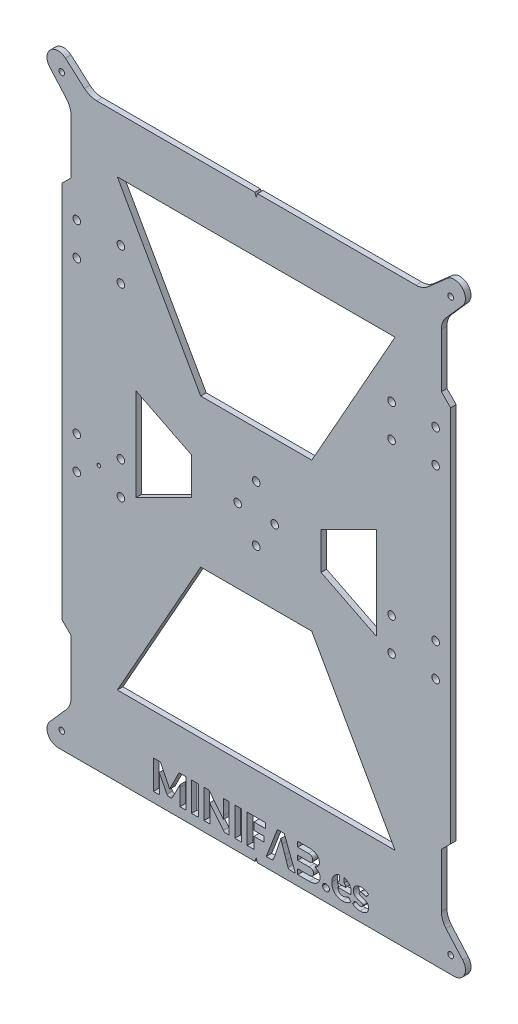
SolidWorks part; units mm, degrees
ref_plane "Front Plane" through (0, 0, 0) normal (0, 0, 1) x (1, 0, 0)
ref_plane "Top Plane" through (0, 0, 0) normal (0, 1, 0) x (1, 0, 0)
ref_plane "Right Plane" through (0, 0, 0) normal (1, 0, 0) x (0, 0, -1)
sketch "Model" plane through (0, 0, 0) normal (0, 0, 1) x (1, 0, 0)
  line L0 (52.095, -156.4121) -> (52.8612, -155.1609)
  line L1 (60.6553, -147.8549) -> (59.9077, -149.0226)
  line L2 (5.4072, -157.6632) -> (11.4282, -142.044)
  line L3 (8.2277, -157.6632) -> (5.4072, -157.6632)
  line L4 (10.3191, -154.1044) -> (9.4016, -156.8693)
  line L5 (11.1501, -151.7319) -> (10.3191, -154.1044)
  line L6 (12.5835, -147.4811) -> (11.1501, -151.7319)
  line L7 (15.4102, -151.7319) -> (13.9706, -147.4594)
  line L8 (16.235, -154.1044) -> (15.4102, -151.7319)
  line L9 (17.1525, -156.8693) -> (16.235, -154.1044)
  line L10 (21.1439, -157.6632) -> (18.3481, -157.6632)
  line L11 (15.1229, -142.044) -> (21.1439, -157.6632)
  line L12 (11.4282, -142.044) -> (15.1229, -142.044)
  line L13 (-11.5929, -157.6632) -> (-11.5929, -142.044)
  line L14 (-7.963, -157.6632) -> (-11.5929, -157.6632)
  line L15 (-7.963, -142.044) -> (-7.963, -157.6632)
  line L16 (-11.5929, -142.044) -> (-7.963, -142.044)
  line L17 (-34.9229, -157.6632) -> (-34.9229, -142.044)
  line L18 (-31.293, -157.6632) -> (-34.9229, -157.6632)
  line L19 (-31.293, -142.044) -> (-31.293, -157.6632)
  line L20 (-34.9229, -142.044) -> (-31.293, -142.044)
  line L21 (30, -40) -> (-30, -40)
  line L22 (-30, -40) -> (-75, -120)
  line L23 (-75, -120) -> (75, -120)
  line L24 (75, -120) -> (30, -40)
  line L25 (30, 40) -> (75, 120)
  line L26 (75, 120) -> (-75, 120)
  line L27 (-75, 120) -> (-30, 40)
  line L28 (-30, 40) -> (30, 40)
  line L29 (-35, 10) -> (-65, 25)
  line L30 (-65, 25) -> (-65, -25)
  line L31 (-65, -25) -> (-35, -10)
  line L32 (-35, -10) -> (-35, 10)
  line L33 (35, -10) -> (65, -25)
  line L34 (65, -25) -> (65, 25)
  line L35 (65, 25) -> (35, 10)
  line L36 (35, 10) -> (35, -10)
  line L37 (-102.5021, -142.8353) -> (-111.4987, -153.0299)
  line L38 (-100, -136.2185) -> (-100, -107)
  line L39 (-105, -102) -> (-100, -107)
  line L40 (-105, 102) -> (-105, -102)
  line L41 (-100, 107) -> (-105, 102)
  line L42 (-100, 107) -> (-100, 136.2185)
  line L43 (-102.5021, 142.8353) -> (-111.4987, 153.0299)
  line L44 (-92.8353, 152.5021) -> (-103.0299, 161.4987)
  line L45 (-86.2185, 150) -> (-0.6974, 150)
  line L46 (-0.6974, 150) -> (0, 148)
  line L47 (0, 148) -> (0.7013, 150)
  line L48 (0.7013, 150) -> (86.2185, 150)
  line L49 (92.8353, 152.5021) -> (103.0299, 161.4987)
  line L50 (102.5021, 142.8353) -> (111.4987, 153.0299)
  line L51 (100, 107) -> (100, 136.2185)
  line L52 (105, 102) -> (100, 107)
  line L53 (105, -102) -> (105, 102)
  line L54 (100, -107) -> (105, -102)
  line L55 (100, -136.2185) -> (100, -107)
  line L56 (102.5021, -142.8353) -> (111.4987, -153.0299)
  line L57 (0.6995, -163) -> (107, -163)
  line L58 (0, -160.9967) -> (0.6995, -163)
  line L59 (-0.7007, -163) -> (0, -160.9967)
  line L60 (-107, -163) -> (-0.7007, -163)
  line L61 (-45.9392, -150.4931) -> (-41.9448, -142.5815)
  line L62 (-51.5338, -142.5815) -> (-47.5301, -150.5271)
  line L63 (-55.4849, -142.044) -> (-52.7293, -142.044)
  line L64 (-55.4849, -157.6632) -> (-55.4849, -142.044)
  line L65 (-52.303, -157.6632) -> (-55.4849, -157.6632)
  line L66 (-52.303, -148.6921) -> (-52.303, -157.6632)
  line L67 (-48.2468, -155.2969) -> (-52.3771, -147.2586)
  line L68 (-46.4952, -156.0568) -> (-46.9864, -156.0568)
  line L69 (-41.1014, -147.2803) -> (-45.2348, -155.2969)
  line L70 (-41.1786, -157.6632) -> (-41.1786, -148.6921)
  line L71 (-37.9967, -157.6632) -> (-41.1786, -157.6632)
  line L72 (-37.9967, -142.044) -> (-37.9967, -157.6632)
  line L73 (-40.7492, -142.044) -> (-37.9967, -142.044)
  line L74 (-25.1022, -142.597) -> (-17.7034, -151.9389)
  line L75 (-28.2007, -142.044) -> (-26.3008, -142.044)
  line L76 (-28.2007, -157.6632) -> (-28.2007, -142.044)
  line L77 (-25.0188, -157.6632) -> (-28.2007, -157.6632)
  line L78 (-25.0188, -149.3253) -> (-25.0188, -157.6632)
  line L79 (-17.759, -157.0639) -> (-25.0929, -147.7869)
  line L80 (-14.6204, -157.6632) -> (-16.4986, -157.6632)
  line L81 (-14.6204, -142.044) -> (-14.6204, -157.6632)
  line L82 (-17.8023, -142.044) -> (-14.6204, -142.044)
  line L83 (-17.8023, -150.2737) -> (-17.8023, -142.044)
  line L84 (-4.8707, -142.044) -> (5.1446, -142.044)
  line L85 (-4.8707, -157.6632) -> (-4.8707, -142.044)
  line L86 (-1.2408, -157.6632) -> (-4.8707, -157.6632)
  line L87 (-1.2408, -151.5342) -> (-1.2408, -157.6632)
  line L88 (4.0758, -151.5342) -> (-1.2408, -151.5342)
  line L89 (4.0758, -148.7662) -> (4.0758, -151.5342)
  line L90 (-1.2408, -148.7662) -> (4.0758, -148.7662)
  line L91 (-1.2408, -144.812) -> (-1.2408, -148.7662)
  line L92 (5.1446, -144.812) -> (-1.2408, -144.812)
  line L93 (5.1446, -142.044) -> (5.1446, -144.812)
  line L94 (28.6291, -157.6632) -> (22.4135, -157.6632)
  line L95 (22.4135, -142.044) -> (28.1379, -142.044)
  line L96 (22.4135, -144.812) -> (22.4135, -142.044)
  line L97 (28.1379, -144.812) -> (22.4135, -144.812)
  line L98 (22.4135, -148.5685) -> (27.9031, -148.5685)
  line L99 (22.4135, -150.941) -> (22.4135, -148.5685)
  line L100 (28.5426, -150.941) -> (22.4135, -150.941)
  line L101 (22.4135, -154.8953) -> (28.5642, -154.8953)
  line L102 (22.4135, -157.6632) -> (22.4135, -154.8953)
  line L103 (44.1711, -150.7433) -> (48.2922, -150.7433)
  line L104 (45.0083, -146.519) -> (45.0083, -149.1628)
  line L105 (50.2353, -154.8397) -> (51.1961, -156.0506)
  line L106 (50.5133, -152.7204) -> (44.1279, -152.7204)
  line L107 (47.5053, -149.0749) -> (47.5053, -146.5108)
  line L108 (-96.9, -11.0958) -> (-73.1, -28.8958) construction
  line L109 (-96.9, -28.8958) -> (-73.1, -11.0958) construction
  circle A0 centre (-96.9, 88.9) radius 2.05
  circle A1 centre (-73.1, 88.9) radius 2.05
  circle A2 centre (-73.1, 71.1) radius 2.05
  circle A3 centre (-96.9, 71.1) radius 2.05
  circle A4 centre (73.1, 88.9) radius 2.05
  circle A5 centre (96.9, 88.9) radius 2.05
  circle A6 centre (96.9, 71.1) radius 2.05
  circle A7 centre (73.1, 71.1) radius 2.05
  circle A8 centre (73.1, -11.0958) radius 2.05
  circle A9 centre (96.9, -11.0958) radius 2.05
  circle A10 centre (96.9, -28.8958) radius 2.05
  circle A11 centre (73.1, -28.8958) radius 2.05
  circle A12 centre (-96.9, -11.0958) radius 2.05
  circle A13 centre (-73.1, -11.0958) radius 2.05
  circle A14 centre (-73.1, -28.8958) radius 2.05
  circle A15 centre (-96.9, -28.8958) radius 2.05
  circle A16 centre (-10, 0) radius 2.05
  circle A17 centre (0, -15) radius 2.05
  circle A18 centre (10, 0) radius 2.05
  circle A19 centre (0, 15) radius 2.05
  circle A20 centre (-105, 154) radius 1.55
  circle A21 centre (105, 154) radius 1.55
  circle A22 centre (105, -154) radius 1.55
  circle A23 centre (-105, -154) radius 1.55
  arc A24 (-102.5021, -142.8353) -> (-100, -136.2185) centre (-110, -136.2185) ccw
  arc A25 (-100, 136.2185) -> (-102.5021, 142.8353) centre (-110, 136.2185) ccw
  arc A26 (-103.0299, 161.4987) -> (-111.4987, 153.0299) centre (-107, 157) ccw
  arc A27 (-92.8353, 152.5021) -> (-86.2185, 150) centre (-86.2185, 160) ccw
  arc A28 (86.2185, 150) -> (92.8353, 152.5021) centre (86.2185, 160) ccw
  arc A29 (111.4987, 153.0299) -> (103.0299, 161.4987) centre (107, 157) ccw
  arc A30 (102.5021, 142.8353) -> (100, 136.2185) centre (110, 136.2185) ccw
  arc A31 (100, -136.2185) -> (102.5021, -142.8353) centre (110, -136.2185) ccw
  arc A32 (107, -163) -> (111.4987, -153.0299) centre (107, -157) ccw
  arc A33 (-111.4987, -153.0299) -> (-107, -163) centre (-107, -157) ccw
  circle A34 centre (-85, -19.9958) radius 1
  spline S0 degree 3 poles (52.4565, -149.8629) (52.4605, -149.7474) (52.4684, -149.5195) (52.518, -149.1813) (52.6066, -148.8543) (52.7221, -148.5336) (52.8782, -148.2294) (53.0625, -147.9384) (53.2887, -147.6736) (53.5423, -147.4229) (53.8354, -147.1987) (54.1603, -146.9922) (54.5238, -146.8189) (54.9186, -146.666) (55.348, -146.5416) (55.8139, -146.4576) (56.3127, -146.404) (56.6567, -146.3972) (56.8339, -146.3937) knots 0 0 0 0 0.055262 0.109055 0.163074 0.217166 0.271812 0.326342 0.381604 0.438049 0.496689 0.557795 0.621919 0.688988 0.760254 0.835436 0.915203 1 1 1 1
  spline S1 degree 3 poles (57.6248, -154.5369) (57.6215, -154.4842) (57.6151, -154.3822) (57.5751, -154.2357) (57.502, -154.1061) (57.3613, -153.9544) (57.1356, -153.7832) (56.8008, -153.6243) (56.4122, -153.4763) (55.9765, -153.3451) (55.5118, -153.2058) (55.0352, -153.049) (54.5598, -152.8591) (54.0905, -152.6465) (53.6471, -152.3805) (53.3207, -152.0997) (53.0878, -151.8451) (52.9333, -151.6293) (52.7948, -151.3948) (52.6717, -151.1399) (52.5767, -150.8587) (52.5045, -150.5518) (52.4663, -150.216) (52.4598, -149.9834) (52.4565, -149.8629) knots 0 0 0 0 0.020827 0.040254 0.05936 0.078936 0.121532 0.170243 0.224662 0.285589 0.349742 0.416188 0.483507 0.55169 0.619371 0.686817 0.720771 0.755403 0.791299 0.828202 0.866889 0.908196 0.952406 1 1 1 1
  spline S2 degree 3 poles (56.2377, -155.4884) (56.3564, -155.4858) (56.575, -155.4811) (56.8761, -155.4231) (57.1192, -155.3279) (57.3141, -155.206) (57.4542, -155.0549) (57.5523, -154.8901) (57.6143, -154.7163) (57.6213, -154.5961) (57.6248, -154.5369) knots 0 0 0 0 0.188683 0.347422 0.484948 0.6022 0.710004 0.809197 0.90609 1 1 1 1
  spline S3 degree 3 poles (53.6953, -154.6883) (53.7871, -154.693) (53.9669, -154.7024) (54.218, -154.8129) (54.457, -154.9509) (54.7153, -155.0978) (55.0091, -155.2363) (55.2806, -155.3491) (55.5289, -155.4221) (55.744, -155.4624) (55.983, -155.4819) (56.1502, -155.4862) (56.2377, -155.4884) knots 0 0 0 0 0.101219 0.198207 0.299998 0.40845 0.527554 0.660406 0.734189 0.814434 0.902797 1 1 1 1
  spline S4 degree 3 poles (52.8612, -155.1609) (52.9075, -155.0924) (52.9975, -154.9594) (53.186, -154.8031) (53.4233, -154.7004) (53.6004, -154.6925) (53.6953, -154.6883) knots 0 0 0 0 0.245291 0.476128 0.719302 1 1 1 1
  spline S5 degree 3 poles (56.0647, -157.8609) (55.876, -157.8556) (55.4966, -157.8448) (54.9323, -157.7574) (54.3784, -157.6242) (53.8415, -157.4529) (53.3339, -157.2409) (52.867, -156.9963) (52.4496, -156.7253) (52.2102, -156.5138) (52.095, -156.4121) knots 0 0 0 0 0.131194 0.263647 0.396161 0.527046 0.655107 0.778099 0.893284 1 1 1 1
  spline S6 degree 3 poles (60.7202, -154.089) (60.7166, -154.223) (60.7095, -154.4881) (60.6541, -154.878) (60.5562, -155.2508) (60.4272, -155.6076) (60.2618, -155.9451) (60.0534, -156.2571) (59.8136, -156.5485) (59.5332, -156.8129) (59.2154, -157.0457) (58.8679, -157.2606) (58.4793, -157.4349) (58.062, -157.5928) (57.6094, -157.7113) (57.1239, -157.7976) (56.6055, -157.8503) (56.2481, -157.8573) (56.0647, -157.8609) knots 0 0 0 0 0.059485 0.117663 0.174315 0.230276 0.285878 0.340645 0.396478 0.453063 0.511205 0.571096 0.634084 0.699887 0.768963 0.841408 0.918592 1 1 1 1
  spline S7 degree 3 poles (55.5951, -149.6744) (55.5966, -149.7243) (55.5995, -149.821) (55.6479, -149.9574) (55.7142, -150.0837) (55.8526, -150.2328) (56.0793, -150.3943) (56.4088, -150.5589) (56.7952, -150.7046) (57.2277, -150.8432) (57.6877, -150.9859) (58.1603, -151.1498) (58.6343, -151.3312) (59.0967, -151.5452) (59.5351, -151.7962) (59.8604, -152.0575) (60.0952, -152.2914) (60.2473, -152.4913) (60.389, -152.7038) (60.5055, -152.9376) (60.605, -153.1907) (60.6692, -153.4697) (60.7157, -153.7713) (60.7187, -153.9806) (60.7202, -154.089) knots 0 0 0 0 0.020281 0.039323 0.058545 0.078231 0.121854 0.17157 0.228495 0.290545 0.357261 0.42544 0.495032 0.564731 0.633624 0.701027 0.734673 0.76887 0.803557 0.838959 0.875478 0.914489 0.955756 1 1 1 1
  spline S8 degree 3 poles (56.8988, -148.7662) (56.7998, -148.7692) (56.6131, -148.7747) (56.3491, -148.816) (56.1222, -148.8924) (55.9314, -148.9983) (55.7804, -149.1316) (55.6704, -149.2913) (55.6073, -149.4764) (55.5993, -149.607) (55.5951, -149.6744) knots 0 0 0 0 0.166013 0.313079 0.446336 0.565434 0.676726 0.781146 0.887098 1 1 1 1
  spline S9 degree 3 poles (59.2683, -149.3964) (59.1893, -149.3917) (59.0281, -149.3821) (58.7908, -149.2984) (58.5492, -149.1889) (58.2847, -149.0766) (57.9937, -148.9635) (57.6683, -148.8608) (57.3004, -148.7759) (57.0374, -148.7695) (56.8988, -148.7662) knots 0 0 0 0 0.095523 0.195146 0.302651 0.418036 0.543856 0.681433 0.832205 1 1 1 1
  spline S10 degree 3 poles (59.9077, -149.0226) (59.8672, -149.0824) (59.7921, -149.1931) (59.6442, -149.321) (59.4637, -149.3861) (59.3367, -149.3928) (59.2683, -149.3964) knots 0 0 0 0 0.277026 0.513154 0.737339 1 1 1 1
  spline S11 degree 3 poles (56.8339, -146.3937) (57.031, -146.3986) (57.4196, -146.4084) (57.9887, -146.4972) (58.5317, -146.6227) (59.0389, -146.8016) (59.5105, -147.0119) (59.9362, -147.2648) (60.323, -147.5388) (60.5464, -147.7513) (60.6553, -147.8549) knots 0 0 0 0 0.14083 0.2778 0.411067 0.538943 0.661888 0.779742 0.89259 1 1 1 1
  spline S12 degree 3 poles (37.696, -154.3021) (37.8247, -154.3075) (38.0767, -154.3179) (38.4325, -154.4354) (38.7566, -154.596) (39.0359, -154.8153) (39.2704, -155.0764) (39.4388, -155.3832) (39.5541, -155.7214) (39.5675, -155.9601) (39.5743, -156.0815) knots 0 0 0 0 0.133864 0.262098 0.387617 0.510223 0.630602 0.751446 0.873527 1 1 1 1
  spline S13 degree 3 poles (35.8178, -156.0815) (35.825, -155.9603) (35.8392, -155.7223) (35.9484, -155.3814) (36.123, -155.0796) (36.3491, -154.8141) (36.6264, -154.5965) (36.9495, -154.4333) (37.3095, -154.3182) (37.5654, -154.3076) (37.696, -154.3021) knots 0 0 0 0 0.126323 0.247933 0.369162 0.487989 0.609604 0.734018 0.864155 1 1 1 1
  spline S14 degree 3 poles (37.696, -157.8609) (37.5656, -157.8549) (37.3106, -157.8431) (36.9491, -157.7371) (36.627, -157.5754) (36.3472, -157.3614) (36.1233, -157.0923) (35.9475, -156.787) (35.84, -156.4426) (35.8253, -156.2027) (35.8178, -156.0815) knots 0 0 0 0 0.135567 0.264836 0.388508 0.509214 0.628614 0.750528 0.873935 1 1 1 1
  spline S15 degree 3 poles (39.5743, -156.0815) (39.5673, -156.2029) (39.5533, -156.4434) (39.4396, -156.7852) (39.2701, -157.0954) (39.0379, -157.3602) (38.7561, -157.5759) (38.4329, -157.7351) (38.0755, -157.8434) (37.8245, -157.855) (37.696, -157.8609) knots 0 0 0 0 0.126216 0.250092 0.371627 0.492568 0.614269 0.739048 0.866408 1 1 1 1
  spline S16 degree 3 poles (9.4016, -156.8693) (9.3794, -156.9195) (9.3347, -157.0208) (9.2377, -157.1618) (9.1211, -157.2981) (8.9798, -157.4225) (8.8214, -157.5342) (8.6379, -157.6061) (8.4394, -157.6558) (8.3001, -157.6607) (8.2277, -157.6632) knots 0 0 0 0 0.109191 0.220141 0.339408 0.465819 0.594408 0.723177 0.856032 1 1 1 1
  spline S17 degree 3 poles (13.2663, -145.3093) (13.2121, -145.5188) (13.1071, -145.925) (12.9326, -146.5017) (12.7586, -147.0162) (12.6389, -147.3341) (12.5835, -147.4811) knots 0 0 0 0 0.284873 0.552589 0.793179 1 1 1 1
  spline S18 degree 3 poles (13.9706, -147.4594) (13.9141, -147.3125) (13.7928, -146.9969) (13.619, -146.4868) (13.4424, -145.9163) (13.3264, -145.5165) (13.2663, -145.3093) knots 0 0 0 0 0.208625 0.448174 0.714092 1 1 1 1
  spline S19 degree 3 poles (18.3481, -157.6632) (18.2738, -157.6599) (18.1313, -157.6535) (17.9268, -157.615) (17.7461, -157.5422) (17.585, -157.4464) (17.4512, -157.3232) (17.3303, -157.1896) (17.2314, -157.0363) (17.1791, -156.9255) (17.1525, -156.8693) knots 0 0 0 0 0.145624 0.279371 0.405263 0.525684 0.644317 0.760102 0.878184 1 1 1 1
  spline S20 degree 3 poles (-46.7393, -152.2787) (-46.678, -152.123) (-46.5562, -151.8135) (-46.366, -151.3568) (-46.165, -150.9147) (-46.0138, -150.6324) (-45.9392, -150.4931) knots 0 0 0 0 0.25634 0.509491 0.757963 1 1 1 1
  spline S21 degree 3 poles (-47.5301, -150.5271) (-47.4591, -150.6656) (-47.3155, -150.9455) (-47.1171, -151.3788) (-46.9208, -151.8227) (-46.8001, -152.1259) (-46.7393, -152.2787) knots 0 0 0 0 0.242868 0.490869 0.743409 1 1 1 1
  spline S22 degree 3 poles (-52.7293, -142.044) (-52.6562, -142.0442) (-52.5192, -142.0444) (-52.3268, -142.0425) (-52.1547, -142.0486) (-52.0035, -142.0953) (-51.8656, -142.1627) (-51.7455, -142.2684) (-51.6292, -142.4062) (-51.5676, -142.5193) (-51.5338, -142.5815) knots 0 0 0 0 0.154412 0.289251 0.407013 0.515754 0.6208 0.728842 0.850807 1 1 1 1
  spline S23 degree 3 poles (-52.3771, -147.2586) (-52.3678, -147.3863) (-52.3494, -147.6385) (-52.3236, -148.0081) (-52.3077, -148.3583) (-52.3045, -148.5839) (-52.303, -148.6921) knots 0 0 0 0 0.26753 0.528471 0.774016 1 1 1 1
  spline S24 degree 3 poles (-46.9864, -156.0568) (-47.0546, -156.0548) (-47.1869, -156.0508) (-47.3793, -156.0102) (-47.5615, -155.9544) (-47.7305, -155.8685) (-47.8867, -155.7615) (-48.0211, -155.6246) (-48.1492, -155.4741) (-48.2138, -155.3569) (-48.2468, -155.2969) knots 0 0 0 0 0.131499 0.255138 0.378409 0.498478 0.619857 0.74221 0.868006 1 1 1 1
  spline S25 degree 3 poles (-45.2348, -155.2969) (-45.2681, -155.3567) (-45.3329, -155.4729) (-45.4572, -155.6267) (-45.5951, -155.7603) (-45.751, -155.8687) (-45.9194, -155.9536) (-46.101, -156.0113) (-46.2938, -156.0504) (-46.4271, -156.0546) (-46.4952, -156.0568) knots 0 0 0 0 0.131962 0.25648 0.380233 0.501583 0.621622 0.742972 0.868533 1 1 1 1
  spline S26 degree 3 poles (-41.1786, -148.6921) (-41.1781, -148.5839) (-41.1772, -148.3593) (-41.1646, -148.0121) (-41.1409, -147.6494) (-41.1146, -147.4038) (-41.1014, -147.2803) knots 0 0 0 0 0.229297 0.476207 0.736652 1 1 1 1
  spline S27 degree 3 poles (-41.9448, -142.5815) (-41.9106, -142.5196) (-41.8487, -142.4077) (-41.7363, -142.2661) (-41.6135, -142.1648) (-41.4777, -142.0943) (-41.3268, -142.0488) (-41.1539, -142.0424) (-40.9604, -142.0445) (-40.8224, -142.0442) (-40.7492, -142.044) knots 0 0 0 0 0.149114 0.26963 0.379287 0.482347 0.59103 0.708729 0.84567 1 1 1 1
  spline S28 degree 3 poles (-17.7034, -151.9389) (-17.7199, -151.7917) (-17.7521, -151.5029) (-17.7829, -151.0763) (-17.7975, -150.6682) (-17.8007, -150.4025) (-17.8023, -150.2737) knots 0 0 0 0 0.266141 0.522245 0.768599 1 1 1 1
  spline S29 degree 3 poles (-26.3008, -142.044) (-26.2287, -142.0452) (-26.0966, -142.0474) (-25.9138, -142.0624) (-25.7558, -142.0879) (-25.6163, -142.1395) (-25.4865, -142.2119) (-25.3626, -142.3131) (-25.2348, -142.4436) (-25.149, -142.5429) (-25.1022, -142.597) knots 0 0 0 0 0.155923 0.285543 0.39647 0.500716 0.605388 0.716315 0.845418 1 1 1 1
  spline S30 degree 3 poles (-25.0929, -147.7869) (-25.0794, -147.9238) (-25.0529, -148.192) (-25.0337, -148.5869) (-25.02, -148.9628) (-25.0192, -149.2069) (-25.0188, -149.3253) knots 0 0 0 0 0.267722 0.524721 0.769439 1 1 1 1
  spline S31 degree 3 poles (-16.4986, -157.6632) (-16.5656, -157.6614) (-16.694, -157.6579) (-16.8782, -157.6327) (-17.0465, -157.5935) (-17.2016, -157.5351) (-17.3439, -157.449) (-17.4879, -157.3486) (-17.6264, -157.2161) (-17.7135, -157.1161) (-17.759, -157.0639) knots 0 0 0 0 0.138412 0.265062 0.383209 0.495001 0.605551 0.725975 0.856911 1 1 1 1
  spline S32 degree 3 poles (34.4585, -152.9305) (34.4536, -153.0945) (34.4438, -153.4188) (34.3716, -153.8965) (34.2507, -154.3576) (34.0802, -154.7981) (33.8675, -155.2181) (33.6048, -155.6099) (33.2988, -155.9751) (32.947, -156.3099) (32.554, -156.6145) (32.113, -156.8803) (31.6315, -157.1148) (31.1073, -157.3125) (30.5431, -157.47) (29.9396, -157.5832) (29.297, -157.6524) (28.8558, -157.6596) (28.6291, -157.6632) knots 0 0 0 0 0.058312 0.115346 0.171406 0.227525 0.283057 0.338524 0.394942 0.452196 0.510953 0.571448 0.635008 0.701199 0.770431 0.84313 0.919377 1 1 1 1
  spline S33 degree 3 poles (31.4465, -149.5323) (31.5704, -149.5653) (31.8125, -149.6296) (32.1619, -149.7415) (32.4836, -149.8761) (32.781, -150.021) (33.0558, -150.1778) (33.3021, -150.3539) (33.524, -150.5445) (33.7232, -150.7479) (33.8955, -150.9692) (34.0501, -151.2018) (34.1754, -151.4525) (34.2786, -151.7184) (34.358, -151.9999) (34.4171, -152.2962) (34.4511, -152.6084) (34.456, -152.8213) (34.4585, -152.9305) knots 0 0 0 0 0.077329 0.151208 0.221133 0.287546 0.350743 0.411776 0.469937 0.52706 0.583245 0.63891 0.695318 0.751973 0.810777 0.871583 0.934091 1 1 1 1
  spline S34 degree 3 poles (34.094, -146.2423) (34.0874, -146.4129) (34.0742, -146.7529) (33.9722, -147.1665) (33.8634, -147.4871) (33.7535, -147.7172) (33.627, -147.9431) (33.4743, -148.157) (33.3056, -148.3672) (33.1062, -148.5604) (32.8927, -148.7542) (32.6492, -148.9311) (32.3876, -149.1037) (32.0956, -149.2561) (31.7834, -149.4067) (31.5605, -149.4898) (31.4465, -149.5323) knots 0 0 0 0 0.112812 0.224796 0.280437 0.336875 0.393375 0.451641 0.510751 0.571506 0.63527 0.701552 0.77059 0.842592 0.919463 1 1 1 1
  spline S35 degree 3 poles (28.1379, -142.044) (28.3965, -142.0474) (28.8947, -142.0539) (29.612, -142.1081) (30.2692, -142.204) (30.8685, -142.3322) (31.4111, -142.4952) (31.9003, -142.6903) (32.3384, -142.9147) (32.7255, -143.1725) (33.0617, -143.4609) (33.3494, -143.7795) (33.5899, -144.1262) (33.7749, -144.5049) (33.916, -144.9069) (34.0233, -145.3303) (34.0803, -145.7794) (34.0894, -146.0856) (34.094, -146.2423) knots 0 0 0 0 0.093616 0.180381 0.260269 0.333916 0.402095 0.465172 0.524374 0.580011 0.633153 0.684371 0.735049 0.785408 0.836474 0.889106 0.943264 1 1 1 1
  spline S36 degree 3 poles (30.4857, -146.6995) (30.4839, -146.6129) (30.4803, -146.4477) (30.4561, -146.2109) (30.414, -145.9962) (30.3508, -145.8033) (30.2753, -145.6267) (30.1744, -145.4727) (30.0598, -145.3328) (29.921, -145.2157) (29.7654, -145.1132) (29.5916, -145.0259) (29.3967, -144.959) (29.1838, -144.9042) (28.9517, -144.8602) (28.6985, -144.8348) (28.4255, -144.8149) (28.2358, -144.813) (28.1379, -144.812) knots 0 0 0 0 0.074123 0.141514 0.203602 0.261051 0.315133 0.367482 0.418179 0.469448 0.522279 0.577492 0.635507 0.698391 0.765672 0.837542 0.916205 1 1 1 1
  spline S37 degree 3 poles (27.9031, -148.5685) (28.0928, -148.5645) (28.4525, -148.5568) (28.8892, -148.5057) (29.2062, -148.4403) (29.4211, -148.3747) (29.6185, -148.2959) (29.7974, -148.1993) (29.9576, -148.0843) (30.096, -147.948) (30.2161, -147.7936) (30.3156, -147.6192) (30.393, -147.4215) (30.4484, -147.2016) (30.4777, -146.9577) (30.483, -146.7881) (30.4857, -146.6995) knots 0 0 0 0 0.154691 0.293488 0.357913 0.418506 0.47654 0.531049 0.583982 0.636855 0.688948 0.743133 0.800075 0.861609 0.927673 1 1 1 1
  spline S38 degree 3 poles (30.8904, -152.8162) (30.8857, -152.6767) (30.8768, -152.4115) (30.8051, -152.0926) (30.7188, -151.8634) (30.6316, -151.7089) (30.5249, -151.5672) (30.3967, -151.4399) (30.2482, -151.3258) (30.0773, -151.2249) (29.884, -151.1402) (29.6675, -151.0694) (29.4275, -151.0088) (29.1583, -150.9716) (28.8602, -150.9462) (28.6518, -150.9428) (28.5426, -150.941) knots 0 0 0 0 0.120625 0.229415 0.281071 0.332162 0.382445 0.434139 0.488171 0.544133 0.605597 0.670441 0.741149 0.819574 0.905459 1 1 1 1
  spline S39 degree 3 poles (28.5642, -154.8953) (28.6786, -154.8928) (28.8966, -154.8882) (29.207, -154.8554) (29.4837, -154.7977) (29.7284, -154.7157) (29.9454, -154.6181) (30.1354, -154.5014) (30.3035, -154.3768) (30.4446, -154.235) (30.5617, -154.0822) (30.6631, -153.921) (30.7387, -153.7473) (30.8172, -153.5068) (30.8744, -153.1947) (30.8851, -152.942) (30.8904, -152.8162) knots 0 0 0 0 0.096124 0.183188 0.261946 0.333101 0.39971 0.461453 0.520129 0.575205 0.628868 0.681708 0.734782 0.787601 0.894192 1 1 1 1
  spline S40 degree 3 poles (45.0083, -149.1628) (44.9621, -149.1982) (44.8223, -149.3171) (44.6191, -149.5582) (44.4193, -149.9025) (44.2636, -150.3016) (44.2028, -150.5918) (44.1711, -150.7433) knots 0.437651 0.437651 0.437651 0.437651 0.491271 0.606533 0.726677 0.857295 1 1 1 1
  spline S41 degree 3 poles (40.8193, -151.8863) (40.8242, -151.7028) (40.834, -151.3385) (40.9067, -150.8008) (41.0248, -150.2777) (41.1879, -149.7716) (41.3961, -149.2874) (41.6527, -148.8338) (41.9453, -148.4091) (42.281, -148.018) (42.6558, -147.6621) (43.0681, -147.3423) (43.5188, -147.0634) (44.0061, -146.8255) (44.5042, -146.6366) (44.8458, -146.5523) (45.0083, -146.519) knots 0 0 0 0 0.063477 0.126005 0.187368 0.248769 0.309722 0.369377 0.42877 0.487891 0.547361 0.607291 0.668089 0.730386 0.79464 0.851966 0.851966 0.851966 0.851966
  spline S42 degree 3 poles (46.4355, -157.8609) (46.2438, -157.8562) (45.8661, -157.8468) (45.3091, -157.7728) (44.7696, -157.6572) (44.2508, -157.4893) (43.7548, -157.2787) (43.2931, -157.0127) (42.8604, -156.7058) (42.4606, -156.3528) (42.097, -155.9525) (41.7762, -155.5039) (41.4893, -155.0142) (41.2492, -154.4766) (41.0515, -153.8945) (40.9202, -153.2637) (40.8336, -152.59) (40.8241, -152.1255) (40.8193, -151.8863) knots 0 0 0 0 0.062244 0.122581 0.182126 0.241125 0.29938 0.356732 0.413787 0.471343 0.529569 0.588957 0.650084 0.713531 0.779821 0.849266 0.922376 1 1 1 1
  spline S43 degree 3 poles (51.1961, -156.0506) (51.1096, -156.1402) (50.9395, -156.3164) (50.6689, -156.5604) (50.386, -156.775) (49.9998, -157.025) (49.4998, -157.2832) (48.8817, -157.5217) (48.2549, -157.6868) (47.6333, -157.7942) (47.0266, -157.8487) (46.6292, -157.8569) (46.4355, -157.8609) knots 0 0 0 0 0.071192 0.139987 0.20805 0.274025 0.402798 0.528977 0.652083 0.772786 0.889256 1 1 1 1
  spline S44 degree 3 poles (49.636, -154.5462) (49.6983, -154.5494) (49.8184, -154.5555) (49.9848, -154.6128) (50.1301, -154.7052) (50.1995, -154.794) (50.2353, -154.8397) knots 0 0 0 0 0.268065 0.516898 0.751167 1 1 1 1
  spline S45 degree 3 poles (46.7321, -155.4884) (46.8249, -155.4868) (47.0047, -155.4838) (47.2635, -155.4544) (47.5045, -155.4143) (47.7899, -155.3256) (48.1128, -155.1996) (48.4613, -155.0262) (48.7709, -154.8515) (49.0544, -154.6897) (49.3393, -154.5678) (49.538, -154.5533) (49.636, -154.5462) knots 0 0 0 0 0.089916 0.174272 0.252418 0.326349 0.463564 0.588155 0.70347 0.808024 0.905378 1 1 1 1
  spline S46 degree 3 poles (44.1279, -152.7204) (44.143, -152.838) (44.1723, -153.066) (44.2368, -153.3933) (44.318, -153.6954) (44.411, -153.9738) (44.5277, -154.2259) (44.6555, -154.4548) (44.8017, -154.659) (44.9673, -154.8345) (45.144, -154.9915) (45.3359, -155.1234) (45.5389, -155.2356) (45.7525, -155.3293) (45.9808, -155.3999) (46.2204, -155.4522) (46.4728, -155.484) (46.6445, -155.4869) (46.7321, -155.4884) knots 0 0 0 0 0.083732 0.162331 0.235376 0.304613 0.369385 0.431275 0.489619 0.546232 0.601382 0.656263 0.710309 0.765035 0.820706 0.878772 0.938136 1 1 1 1
  spline S47 degree 3 poles (51.2609, -151.4878) (51.2593, -151.6012) (51.2564, -151.8056) (51.233, -152.0804) (51.1948, -152.3006) (51.1206, -152.4695) (51.0175, -152.5972) (50.8783, -152.678) (50.7058, -152.7154) (50.5815, -152.7186) (50.5133, -152.7204) knots 0 0 0 0 0.201814 0.363871 0.491198 0.5979 0.689011 0.778652 0.878735 1 1 1 1
  spline S48 degree 3 poles (47.5053, -146.5108) (47.6139, -146.5321) (47.8814, -146.5928) (48.295, -146.7288) (48.7364, -146.9186) (49.1479, -147.1488) (49.5272, -147.418) (49.8709, -147.7301) (50.185, -148.076) (50.4597, -148.4616) (50.7005, -148.8822) (50.8988, -149.341) (51.0652, -149.8306) (51.1768, -150.3563) (51.2509, -150.9111) (51.2575, -151.2929) (51.2609, -151.4878) knots 0.152869 0.152869 0.152869 0.152869 0.194178 0.255214 0.315138 0.37332 0.43093 0.488371 0.546355 0.605039 0.664792 0.72694 0.791378 0.857517 0.927285 1 1 1 1
  spline S49 degree 3 poles (48.2922, -150.7433) (48.2876, -150.6204) (48.2785, -150.3751) (48.1996, -150.0172) (48.07, -149.6784) (47.9015, -149.4283) (47.7385, -149.2503) (47.6153, -149.1508) (47.5354, -149.0947) (47.5053, -149.0749) knots 0 0 0 0 0.117376 0.234157 0.348558 0.462105 0.519901 0.57862 0.613071 0.613071 0.613071 0.613071
  point P226 (-85, -19.9958)
extrude "Saliente-Extruir1" add sketch "Model" along normal blind 3
